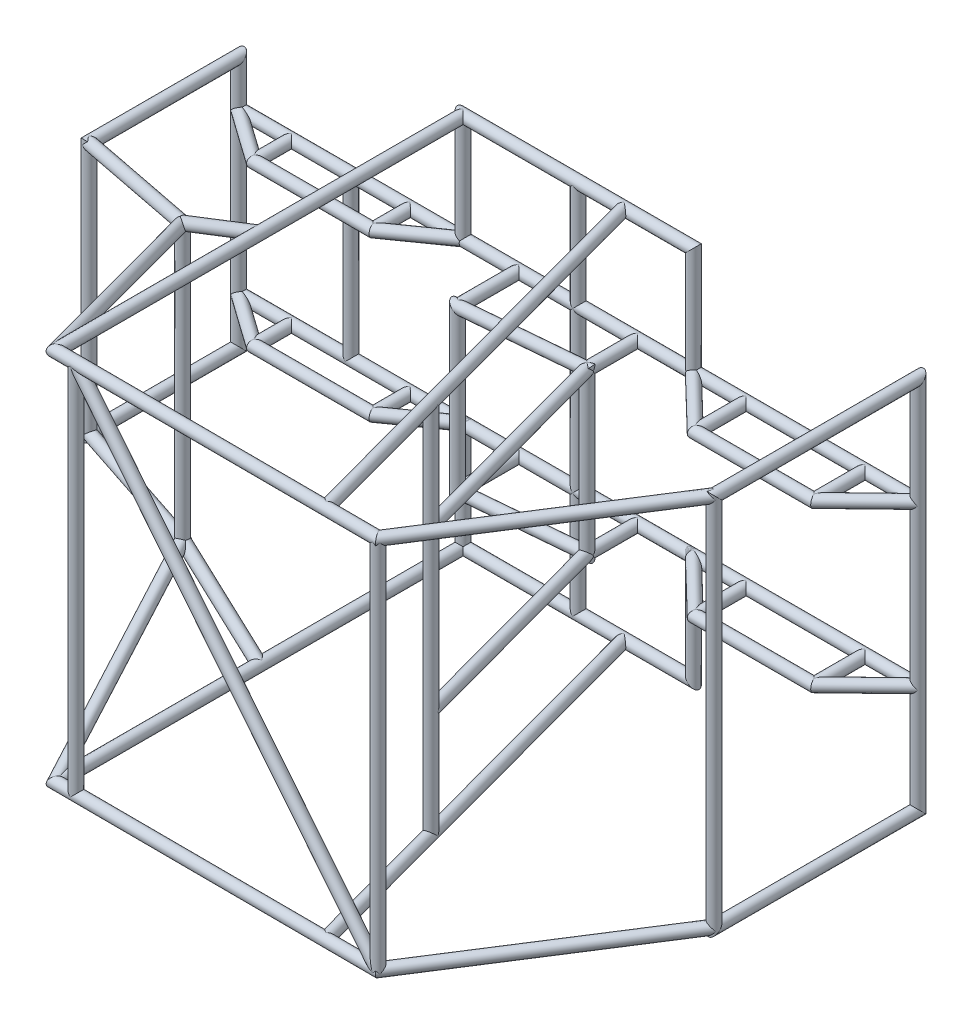
SolidWorks part; units mm, degrees
other "Markup1"
sketch "Sketch117" plane through (1036.7339, -482.8357, 1175.9129) normal (0.0347, -0.967, 0.2524) x (0.9983, 0.0455, 0.0372)
other "Markup2"
sketch "Sketch1172" plane through (1036.7339, -482.8357, 1116.7005) normal (0.0129, -0.9746, 0.2236) x (0.9995, 0.0192, 0.026)
other "Markup3"
sketch "Sketch1173" plane through (-996.6671, 650.5653, 1116.7005) normal (-0.8943, 0.014, 0.4473) x (0.1458, -0.9359, 0.3207)
other "Markup4"
sketch "Sketch1174" plane through (-996.6671, 650.5653, 1116.7005) normal (-0.8943, 0.014, 0.4473) x (0.1458, -0.9359, 0.3207)
other "Markup5"
sketch "Sketch1192" plane through (-996.6671, -482.8357, 1116.7005) normal (-0.3732, -0.8965, 0.2388) x (0.9278, -0.3613, 0.0935)
other "Markup6"
sketch "Sketch1210" plane through (-996.6671, -486.1883, 1216.7017) normal (-0.3761, -0.9216, 0.0957) x (0.9265, -0.373, 0.0487)
material "AISI 1020 Steel, Cold Rolled"
ref_plane "Front Plane" through (0, 0, 0) normal (0, 0, 1) x (1, 0, 0)
ref_plane "Top Plane" through (0, 0, 0) normal (0, 1, 0) x (1, 0, 0)
ref_plane "Right Plane" through (0, 0, 0) normal (1, 0, 0) x (0, 0, -1)
sketch "Sketch1" plane through (0, 0, 0) normal (0, 0, 1) x (1, 0, 0)
  line L1 (1020.0334, 633.8648) -> (1020.0334, -466.1352) construction
  line L4 (-979.9666, -286.1352) -> (-979.9666, 453.8648)
  line L5 (-979.9666, 318.8648) -> (-318.9666, 318.8648)
  line L6 (-318.9666, 318.8648) -> (-318.9666, 633.8648)
  line L7 (-318.9666, 633.8648) -> (359.0334, 633.8648)
  line L8 (359.0334, 633.8648) -> (359.0334, 318.8648)
  line L9 (359.0334, 318.8648) -> (1020.0334, 318.8648)
  line L10 (-979.9666, 83.8648) -> (1020.0334, 83.8648) construction
  line L11 (359.0334, -151.1352) -> (1020.0334, -151.1352)
  line L12 (359.0334, -466.1352) -> (359.0334, -151.1352)
  line L13 (-318.9666, -466.1352) -> (359.0334, -466.1352)
  line L14 (-318.9666, -151.1352) -> (-318.9666, -466.1352)
  line L15 (-979.9666, -151.1352) -> (-318.9666, -151.1352)
  line L18 (1020.0334, 633.8648) -> (1020.0334, -466.1352)
  dimension "D1" = 678
  dimension "D2" = 1100
  dimension "D3" = 315
  dimension "D4" = 661
  dimension "D5" = 661
  dimension "D6" = 315
  dimension "D7" = 370
  dimension "D8" = 370
sketch3d "3DSketch1"
  line L1 (-979.9666, -286.1352, 0) -> (-979.9666, -286.1352, 440)
  line L12 (-979.9666, 453.8648, 0) -> (-979.9666, 453.8648, 440)
  line L14 (1020.0334, -466.1352, 0) -> (1020.0334, -466.1352, 600)
  line L15 (1020.0334, 633.8648, 0) -> (1020.0334, -466.1352, 0) construction
  line L16 (1020.0334, 633.8648, 0) -> (1020.0334, 633.8648, 600)
  line L32 (-318.9666, -466.1352, 0) -> (-318.9666, -466.1352, 1200)
  line L35 (1020.0334, -466.1352, 600) -> (1020.0334, 633.8648, 600)
  line L37 (-318.9666, 633.8648, 0) -> (-318.9666, 633.8648, 1200)
  line L44 (-979.9666, 453.8648, 440) -> (-979.9666, -286.1352, 440)
  line L59 (-318.9666, -466.1352, 0) -> (359.0334, -466.1352, 0) construction
  line L61 (-824.4666, -151.1352, 110) -> (-979.9666, -151.1352, 0)
  line L62 (-649.4666, 318.8648, 0) -> (-649.4666, -151.1352, 0)
  line L63 (-979.9666, 318.8648, 0) -> (-318.9666, 318.8648, 0) construction
  line L64 (-979.9666, -151.1352, 0) -> (-318.9666, -151.1352, 0) construction
  line L65 (359.0334, -151.1352, 0) -> (1020.0334, -151.1352, 0) construction
  line L66 (359.0334, 318.8648, 0) -> (1020.0334, 318.8648, 0) construction
  line L77 (20.0334, -466.1352, 0) -> (20.0334, 633.8648, 0)
  line L78 (-318.9666, 633.8648, 0) -> (359.0334, 633.8648, 0) construction
  line L101 (195.0334, -151.1352, 0) -> (195.0334, -151.1352, 149.379)
  line L102 (-318.9666, -151.1352, 0) -> (359.0334, -151.1352, 0)
  line L103 (195.0334, 318.8648, 0) -> (195.0334, 318.8648, 149.379)
  line L113 (-318.9666, 318.8648, 0) -> (359.0334, 318.8648, 0)
  line L127 (-154.9666, -151.1352, 180) -> (-154.9666, 318.8648, 180)
  line L130 (-154.9666, -151.1352, 0) -> (-154.9666, -151.1352, 180)
  line L131 (-154.9666, 318.8648, 0) -> (-154.9666, 318.8648, 180)
  line L132 (-154.9666, 318.8648, 180) -> (195.0334, 318.8648, 149.379)
  line L133 (-154.9666, -151.1352, 180) -> (195.0334, -151.1352, 149.379)
  line L134 (195.0334, -151.1352, 149.379) -> (195.0334, 318.8648, 149.379)
  line L135 (195.0334, -151.1352, 149.379) -> (195.0334, -151.1352, 921.293) construction
  line L136 (195.0334, 318.8648, 149.379) -> (195.0334, 318.8648, 894.0715) construction
  line L137 (195.0334, -151.1352, 149.379) -> (363.2555, -152.9932, 777.2308)
  line L138 (195.0334, 318.8648, 149.379) -> (363.2555, 317.0068, 777.2308)
  line L144 (-318.9666, -466.1352, 1200) -> (886.7474, -466.1352, 1200) construction
  line L145 (195.0334, 83.8648, 149.379) -> (363.2555, 82.0068, 777.2308) construction
  line L151 (-318.9666, 633.8648, 1200) -> (870.5373, 633.8648, 1200) construction
  line L152 (631.0272, -469.5609, 1200.0013) -> (1020.0334, -466.1352, 600)
  line L153 (631.0272, 630.4391, 1200.0013) -> (1020.0334, 633.8648, 600)
  line L154 (-258.9666, 633.8648, 1200) -> (-258.9666, -466.1352, 1200)
  line L155 (-318.9666, -466.1352, 1200) -> (631.0272, -469.5609, 1200.0013)
  line L156 (-318.9666, 633.8648, 1200) -> (631.0272, 630.4391, 1200.0013)
  line L157 (631.0272, -469.5609, 1200.0013) -> (631.0272, 630.4391, 1200.0013)
  line L158 (-258.9666, 633.8648, 1200) -> (631.0272, -469.5609, 1200.0013)
  line L159 (154.9966, -466.1352, 0) -> (476.5368, -469.0038, 1200.0011)
  line L160 (363.2555, -467.9932, 777.2308) -> (363.2555, 632.0068, 777.2308)
  line L162 (476.5368, 630.9962, 1200.0011) -> (154.9966, 633.8648, 0)
  line L165 (-602.9909, 488.0187, 541.424) -> (-318.9666, 633.8648, 1200)
  line L166 (-602.9933, -320.2889, 541.4234) -> (-318.9666, -466.1352, 1200)
  line L171 (-602.9909, 488.0187, 541.424) -> (-602.9933, -320.2889, 541.4234)
  line L172 (-979.9666, 453.8648, 440) -> (-602.9909, 488.0187, 541.424)
  line L173 (-979.9666, -286.1352, 440) -> (-602.9933, -320.2889, 541.4234)
  line L174 (-602.9933, -320.2889, 541.4234) -> (-318.9666, -466.1352, 600)
  line L175 (-602.9909, 488.0187, 541.424) -> (-318.9666, 633.8648, 600)
  line L178 (-824.4666, -151.1352, 0) -> (-824.4666, -151.1352, 110)
  line L179 (-824.4666, -151.1352, 110) -> (-474.4666, -151.1352, 110)
  line L180 (-474.4666, -151.1352, 110) -> (-474.4666, -151.1352, 0)
  line L181 (-474.4666, 318.8648, 0) -> (-474.4666, 318.8648, 110)
  line L182 (-474.4666, 318.8648, 110) -> (-824.4666, 318.8648, 110)
  line L183 (514.5334, -151.1352, 0) -> (514.5334, -151.1352, 150)
  line L184 (514.5334, -151.1352, 150) -> (864.5334, -151.1352, 150)
  line L185 (864.5334, -151.1352, 150) -> (864.5334, -151.1352, 0)
  line L187 (864.5334, 318.8648, 0) -> (864.5334, 318.8648, 150)
  line L188 (864.5334, 318.8648, 150) -> (514.5334, 318.8648, 150)
  line L189 (514.5334, 318.8648, 150) -> (514.5334, 318.8648, 0)
  line L190 (-824.4666, 318.8648, 110) -> (-824.4666, 318.8648, 0)
  line L191 (-318.9666, 633.8648, 1200) -> (-318.9666, -466.1352, 1200) construction
  line L192 (-474.4666, -151.1352, 110) -> (-318.9666, -151.1352, 0)
  line L193 (514.5334, -151.1352, 150) -> (359.0334, -151.1352, 0)
  line L194 (864.5334, -151.1352, 150) -> (1020.0334, -151.1352, 0)
  line L195 (-824.4666, 318.8648, 110) -> (-979.9666, 318.8648, 0)
  line L196 (-474.4666, 318.8648, 110) -> (-318.9666, 318.8648, 0)
  line L197 (514.5334, 318.8648, 150) -> (359.0334, 318.8648, 0)
  line L198 (864.5334, 318.8648, 150) -> (1020.0334, 318.8648, 0)
  dimension "D3" = 440
  dimension "D2" = 440
  dimension "D9" = 60
  dimension "D4" = 1200
  dimension "D5" = 1200
  dimension "D6" = 60
  dimension "D7" = 600
  dimension "D8" = 600
  dimension "D10" = 1100
  dimension "D15" = 175
  dimension "D11" = 550
  dimension "D12" = 15
  dimension "D13" = 650
  dimension "D14" = 175
  dimension "D18" = 175
  dimension "D16" = 950
  dimension "D17" = 950
  dimension "D19" = 180
  dimension "D35" = 175
  dimension "D26" = 235
  dimension "D29" = 105
  dimension "D28" = 75
  dimension "D20" = 180
  dimension "D21" = 85
  dimension "D22" = 85
  dimension "D23" = 235
  dimension "D24" = 15
  dimension "D25" = 1100
  dimension "D27" = 75
  dimension "D32" = 95
  dimension "D30" = 105
  dimension "D31" = 95
  dimension "D33" = 391.87
  dimension "D34" = 350
  dimension "D36" = 150
  dimension "D45" = 110
  dimension "D39" = 110
  dimension "D37" = 350
  dimension "D40" = 175
  dimension "D41" = 350
  dimension "D42" = 150
  dimension "D43" = 350
other "Pipe 1.0 SCH 40(15)" corner treatment miter
ref_plane "Plane17" through (-979.9666, -151.1352, 0) normal (1, 0, 0) x (0, 1, 0)
sketch "Sketch1171" plane through (-979.9666, -151.1352, 0) normal (1, 0, 0) x (0, 1, 0)
  circle A0 centre (0, 0) radius 13.3223
  circle A1 centre (0, 0) radius 16.7005
  circle A2 centre (0, 0) radius 12.7 construction
  point P5 (0, 16.7005)
  point P6 (0, -16.7005)
  point P7 (-16.7005, 0)
  point P8 (16.7005, 0)
  point P9 (0, 0)
  dimension "In_dia" = 26.6446
  dimension "Out_dia" = 33.401
  dimension "D1" = 25.4
other "Pipe 1.0 SCH 40(16)" corner treatment miter
ref_plane "Plane18" through (-979.9666, 318.8648, 0) normal (1, 0, 0) x (0, 1, 0)
sketch "Sketch118" plane through (-979.9666, 318.8648, 0) normal (1, 0, 0) x (0, 1, 0)
  circle A0 centre (0, 0) radius 13.3223
  circle A1 centre (0, 0) radius 16.7005
  circle A2 centre (0, 0) radius 12.7 construction
  point P5 (0, 16.7005)
  point P6 (0, -16.7005)
  point P7 (-16.7005, 0)
  point P8 (16.7005, 0)
  point P9 (0, 0)
  dimension "In_dia" = 26.6446
  dimension "Out_dia" = 33.401
  dimension "D1" = 25.4
other "Pipe 1.0 SCH 40(18)" corner treatment miter
ref_plane "Plane20" through (-979.9666, -286.1352, 0) normal (0, 0, 1) x (1, 0, 0)
sketch "Sketch120" plane through (-979.9666, -286.1352, 0) normal (0, 0, 1) x (1, 0, 0)
  circle A0 centre (0, 0) radius 13.3223
  circle A1 centre (0, 0) radius 16.7005
  circle A2 centre (0, 0) radius 12.7 construction
  point P5 (0, 16.7005)
  point P6 (0, -16.7005)
  point P7 (-16.7005, 0)
  point P8 (16.7005, 0)
  point P9 (0, 0)
  dimension "In_dia" = 26.6446
  dimension "Out_dia" = 33.401
  dimension "D1" = 25.4
other "Pipe 1.0 SCH 40(19)" corner treatment miter
ref_plane "Plane21" through (1020.0334, -466.1352, 0) normal (0, 0, 1) x (1, 0, 0)
sketch "Sketch121" plane through (1020.0334, -466.1352, 0) normal (0, 0, 1) x (1, 0, 0)
  circle A0 centre (0, 0) radius 13.3223
  circle A1 centre (0, 0) radius 16.7005
  circle A2 centre (0, 0) radius 12.7 construction
  point P5 (0, 16.7005)
  point P6 (0, -16.7005)
  point P7 (-16.7005, 0)
  point P8 (16.7005, 0)
  point P9 (0, 0)
  dimension "In_dia" = 26.6446
  dimension "Out_dia" = 33.401
  dimension "D1" = 25.4
other "Pipe 1.0 SCH 40(30)" corner treatment miter
ref_plane "Plane34" through (20.0334, -466.1352, 0) normal (0, 1, 0) x (1, 0, 0)
sketch "Sketch134" plane through (20.0334, -466.1352, 0) normal (0, 1, 0) x (1, 0, 0)
  circle A0 centre (0, 0) radius 13.3223
  circle A1 centre (0, 0) radius 16.7005
  circle A2 centre (0, 0) radius 12.7 construction
  point P5 (0, 16.7005)
  point P6 (0, -16.7005)
  point P7 (-16.7005, 0)
  point P8 (16.7005, 0)
  point P9 (0, 0)
  dimension "In_dia" = 26.6446
  dimension "Out_dia" = 33.401
  dimension "D1" = 25.4
other "Pipe 1.0 SCH 40(107)" corner treatment miter
ref_plane "Plane57" through (-318.9666, 633.8648, 0) normal (0, 0, 1) x (1, 0, 0)
sketch "Sketch1186" plane through (-318.9666, 633.8648, 0) normal (0, 0, 1) x (1, 0, 0)
  circle A0 centre (0, 0) radius 13.3223
  circle A1 centre (0, 0) radius 16.7005
  circle A2 centre (0, 0) radius 12.7 construction
  point P5 (0, 16.7005)
  point P6 (0, -16.7005)
  point P7 (-16.7005, 0)
  point P8 (16.7005, 0)
  point P9 (0, 0)
  dimension "In_dia" = 26.6446
  dimension "Out_dia" = 33.401
  dimension "D1" = 25.4
other "Pipe 1.0 SCH 40(108)" corner treatment miter
ref_plane "Plane58" through (-318.9666, -151.1352, 0) normal (1, 0, 0) x (0, 0, -1)
sketch "Sketch1187" plane through (-318.9666, -151.1352, 0) normal (1, 0, 0) x (0, 0, -1)
  circle A0 centre (0, 0) radius 13.3223
  circle A1 centre (0, 0) radius 16.7005
  circle A2 centre (0, 0) radius 12.7 construction
  point P5 (0, 16.7005)
  point P6 (0, -16.7005)
  point P7 (-16.7005, 0)
  point P8 (16.7005, 0)
  point P9 (0, 0)
  dimension "In_dia" = 26.6446
  dimension "Out_dia" = 33.401
  dimension "D1" = 25.4
other "Pipe 1.0 SCH 40(109)" corner treatment miter
ref_plane "Plane59" through (-154.9666, -151.1352, 180) normal (0.9962, 0, -0.0872) x (-0.0872, 0, -0.9962)
sketch "Sketch1188" plane through (-154.9666, -151.1352, 180) normal (0.9962, 0, -0.0872) x (-0.0872, 0, -0.9962)
  circle A0 centre (0, 0) radius 13.3223
  circle A1 centre (0, 0) radius 16.7005
  circle A2 centre (0, 0) radius 12.7 construction
  point P5 (0, 16.7005)
  point P6 (0, -16.7005)
  point P7 (-16.7005, 0)
  point P8 (16.7005, 0)
  point P9 (0, 0)
  dimension "In_dia" = 26.6446
  dimension "Out_dia" = 33.401
  dimension "D1" = 25.4
other "Pipe 1.0 SCH 40(168)" corner treatment miter
ref_plane "Plane67" through (-154.9666, -151.1352, 0) normal (0, 0, 1) x (1, 0, 0)
sketch "Sketch1198" plane through (-154.9666, -151.1352, 0) normal (0, 0, 1) x (1, 0, 0)
  circle A0 centre (0, 0) radius 13.3223
  circle A1 centre (0, 0) radius 16.7005
  circle A2 centre (0, 0) radius 12.7 construction
  point P5 (0, 16.7005)
  point P6 (0, -16.7005)
  point P7 (-16.7005, 0)
  point P8 (16.7005, 0)
  point P9 (0, 0)
  dimension "In_dia" = 26.6446
  dimension "Out_dia" = 33.401
  dimension "D1" = 25.4
other "Pipe 1.0 SCH 40(207)" corner treatment miter
ref_plane "Plane70" through (-258.9666, 633.8648, 1200) normal (0, -1, 0) x (1, 0, 0)
sketch "Sketch1202" plane through (-258.9666, 633.8648, 1200) normal (0, -1, 0) x (1, 0, 0)
  circle A0 centre (0, 0) radius 13.3223
  circle A1 centre (0, 0) radius 16.7005
  circle A2 centre (0, 0) radius 12.7 construction
  point P5 (0, 16.7005)
  point P6 (0, -16.7005)
  point P7 (-16.7005, 0)
  point P8 (16.7005, 0)
  point P9 (0, 0)
  dimension "In_dia" = 26.6446
  dimension "Out_dia" = 33.401
  dimension "D1" = 25.4
other "Pipe 1.0 SCH 40(208)" corner treatment miter
ref_plane "Plane71" through (-258.9666, 633.8648, 1200) normal (0.6278, -0.7784, 0) x (0.6059, 0.4887, -0.6278)
sketch "Sketch1203" plane through (-258.9666, 633.8648, 1200) normal (0.6278, -0.7784, 0) x (0.6059, 0.4887, -0.6278)
  circle A0 centre (0, 0) radius 13.3223
  circle A1 centre (0, 0) radius 16.7005
  circle A2 centre (0, 0) radius 12.7 construction
  point P5 (0, 16.7005)
  point P6 (0, -16.7005)
  point P7 (-16.7005, 0)
  point P8 (16.7005, 0)
  point P9 (0, 0)
  dimension "In_dia" = 26.6446
  dimension "Out_dia" = 33.401
  dimension "D1" = 25.4
other "Pipe 1.0 SCH 40(209)" corner treatment miter
ref_plane "Plane72" through (476.5368, 630.9962, 1200.0011) normal (-0.2588, 0.0023, -0.9659) x (-0.9658, 0.0175, 0.2588)
sketch "Sketch1204" plane through (476.5368, 630.9962, 1200.0011) normal (-0.2588, 0.0023, -0.9659) x (-0.9658, 0.0175, 0.2588)
  circle A0 centre (0, 0) radius 13.3223
  circle A1 centre (0, 0) radius 16.7005
  circle A2 centre (0, 0) radius 12.7 construction
  point P5 (0, 16.7005)
  point P6 (0, -16.7005)
  point P7 (-16.7005, 0)
  point P8 (16.7005, 0)
  point P9 (0, 0)
  dimension "In_dia" = 26.6446
  dimension "Out_dia" = 33.401
  dimension "D1" = 25.4
other "Pipe 1.0 SCH 40(210)" corner treatment miter
ref_plane "Plane73" through (363.2555, -467.9932, 777.2308) normal (0, 1, 0) x (1, 0, 0)
sketch "Sketch1205" plane through (363.2555, -467.9932, 777.2308) normal (0, 1, 0) x (1, 0, 0)
  circle A0 centre (0, 0) radius 13.3223
  circle A1 centre (0, 0) radius 16.7005
  circle A2 centre (0, 0) radius 12.7 construction
  point P5 (0, 16.7005)
  point P6 (0, -16.7005)
  point P7 (-16.7005, 0)
  point P8 (16.7005, 0)
  point P9 (0, 0)
  dimension "In_dia" = 26.6446
  dimension "Out_dia" = 33.401
  dimension "D1" = 25.4
other "Pipe 1.0 SCH 40(234)" corner treatment miter
ref_plane "Plane74" through (195.0334, 318.8648, 149.379) normal (0.2588, -0.0029, 0.9659) x (0.9659, 0.0004, -0.2588)
sketch "Sketch1207" plane through (195.0334, 318.8648, 149.379) normal (0.2588, -0.0029, 0.9659) x (0.9659, 0.0004, -0.2588)
  circle A0 centre (0, 0) radius 13.3223
  circle A1 centre (0, 0) radius 16.7005
  circle A2 centre (0, 0) radius 12.7 construction
  point P5 (0, 16.7005)
  point P6 (0, -16.7005)
  point P7 (-16.7005, 0)
  point P8 (16.7005, 0)
  point P9 (0, 0)
  dimension "In_dia" = 26.6446
  dimension "Out_dia" = 33.401
  dimension "D1" = 25.4
other "Pipe 1.0 SCH 40(235)" corner treatment miter
ref_plane "Plane75" through (195.0334, -151.1352, 149.379) normal (0.2588, -0.0029, 0.9659) x (0.9659, 0.0004, -0.2588)
sketch "Sketch1208" plane through (195.0334, -151.1352, 149.379) normal (0.2588, -0.0029, 0.9659) x (0.9659, 0.0004, -0.2588)
  circle A0 centre (0, 0) radius 13.3223
  circle A1 centre (0, 0) radius 16.7005
  circle A2 centre (0, 0) radius 12.7 construction
  point P5 (0, 16.7005)
  point P6 (0, -16.7005)
  point P7 (-16.7005, 0)
  point P8 (16.7005, 0)
  point P9 (0, 0)
  dimension "In_dia" = 26.6446
  dimension "Out_dia" = 33.401
  dimension "D1" = 25.4
other "Pipe 1.0 SCH 40(351)" corner treatment miter
ref_plane "Plane76" through (-979.9666, -286.1352, 440) normal (0.962, -0.0872, 0.2588) x (0.2649, 0.0666, -0.962)
sketch "Sketch1212" plane through (-979.9666, -286.1352, 440) normal (0.962, -0.0872, 0.2588) x (0.2649, 0.0666, -0.962)
  circle A0 centre (0, 0) radius 13.3223
  circle A1 centre (0, 0) radius 16.7005
  circle A2 centre (0, 0) radius 12.7 construction
  point P5 (0, 16.7005)
  point P6 (0, -16.7005)
  point P7 (-16.7005, 0)
  point P8 (16.7005, 0)
  point P9 (0, 0)
  dimension "In_dia" = 26.6446
  dimension "Out_dia" = 33.401
  dimension "D1" = 25.4
other "Pipe 1.0 SCH 40(352)" corner treatment miter
ref_plane "Plane77" through (-979.9666, 453.8648, 440) normal (0.962, 0.0872, 0.2588) x (0.2649, -0.0666, -0.962)
sketch "Sketch1213" plane through (-979.9666, 453.8648, 440) normal (0.962, 0.0872, 0.2588) x (0.2649, -0.0666, -0.962)
  circle A0 centre (0, 0) radius 13.3223
  circle A1 centre (0, 0) radius 16.7005
  circle A2 centre (0, 0) radius 12.7 construction
  point P5 (0, 16.7005)
  point P6 (0, -16.7005)
  point P7 (-16.7005, 0)
  point P8 (16.7005, 0)
  point P9 (0, 0)
  dimension "In_dia" = 26.6446
  dimension "Out_dia" = 33.401
  dimension "D1" = 25.4
other "Pipe 1.0 SCH 40(353)" corner treatment miter
ref_plane "Plane78" through (-602.9909, 488.0187, 541.424) normal (0, -1, 0) x (1, 0, 0)
sketch "Sketch1214" plane through (-602.9909, 488.0187, 541.424) normal (0, -1, 0) x (1, 0, 0)
  circle A0 centre (0, 0) radius 13.3223
  circle A1 centre (0, 0) radius 16.7005
  circle A2 centre (0, 0) radius 12.7 construction
  point P5 (0, 16.7005)
  point P6 (0, -16.7005)
  point P7 (-16.7005, 0)
  point P8 (16.7005, 0)
  point P9 (0, 0)
  dimension "In_dia" = 26.6446
  dimension "Out_dia" = 33.401
  dimension "D1" = 25.4
other "Pipe 1.0 SCH 40(368)" corner treatment miter
ref_plane "Plane79" through (-602.9933, -320.2889, 541.4234) normal (0.875, -0.4493, 0.1805) x (0.3515, 0.333, -0.875)
sketch "Sketch1215" plane through (-602.9933, -320.2889, 541.4234) normal (0.875, -0.4493, 0.1805) x (0.3515, 0.333, -0.875)
  circle A0 centre (0, 0) radius 13.3223
  circle A1 centre (0, 0) radius 16.7005
  circle A2 centre (0, 0) radius 12.7 construction
  point P5 (0, 16.7005)
  point P6 (0, -16.7005)
  point P7 (-16.7005, 0)
  point P8 (16.7005, 0)
  point P9 (0, 0)
  dimension "In_dia" = 26.6446
  dimension "Out_dia" = 33.401
  dimension "D1" = 25.4
other "Pipe 1.0 SCH 40(369)" corner treatment miter
ref_plane "Plane80" through (-602.9909, 488.0187, 541.424) normal (0.875, 0.4493, 0.1804) x (0.3515, -0.333, -0.875)
sketch "Sketch1216" plane through (-602.9909, 488.0187, 541.424) normal (0.875, 0.4493, 0.1804) x (0.3515, -0.333, -0.875)
  circle A0 centre (0, 0) radius 13.3223
  circle A1 centre (0, 0) radius 16.7005
  circle A2 centre (0, 0) radius 12.7 construction
  point P5 (0, 16.7005)
  point P6 (0, -16.7005)
  point P7 (-16.7005, 0)
  point P8 (16.7005, 0)
  point P9 (0, 0)
  dimension "In_dia" = 26.6446
  dimension "Out_dia" = 33.401
  dimension "D1" = 25.4
ref_plane "Plane86" through (-649.4666, 318.8648, 0) normal (0, -1, 0) x (1, 0, 0)
other "Pipe 1.0 SCH 40(501)" corner treatment miter
ref_plane "Plane87" through (-649.4666, 318.8648, 0) normal (0, -1, 0) x (1, 0, 0)
sketch "Sketch1225" plane through (-649.4666, 318.8648, 0) normal (0, -1, 0) x (1, 0, 0)
  circle A0 centre (0, 0) radius 13.3223
  circle A1 centre (0, 0) radius 16.7005
  circle A2 centre (0, 0) radius 12.7 construction
  point P5 (0, 16.7005)
  point P6 (0, -16.7005)
  point P7 (-16.7005, 0)
  point P8 (16.7005, 0)
  point P9 (0, 0)
  dimension "In_dia" = 26.6446
  dimension "Out_dia" = 33.401
  dimension "D1" = 25.4
other "Pipe 1.0 SCH 40(533)" corner treatment miter
ref_plane "Plane92" through (-824.4666, 318.8648, 110) normal (-0.8164, 0, -0.5775) x (-0.5775, 0, 0.8164)
sketch "Sketch1231" plane through (-824.4666, 318.8648, 110) normal (-0.8164, 0, -0.5775) x (-0.5775, 0, 0.8164)
  circle A0 centre (0, 0) radius 13.3223
  circle A1 centre (0, 0) radius 16.7005
  circle A2 centre (0, 0) radius 12.7 construction
  point P5 (0, 16.7005)
  point P6 (0, -16.7005)
  point P7 (-16.7005, 0)
  point P8 (16.7005, 0)
  point P9 (0, 0)
  dimension "In_dia" = 26.6446
  dimension "Out_dia" = 33.401
  dimension "D1" = 25.4
other "Pipe 1.0 SCH 40(534)" corner treatment miter
ref_plane "Plane93" through (-824.4666, -151.1352, 110) normal (-0.8164, 0, -0.5775) x (-0.5775, 0, 0.8164)
sketch "Sketch1232" plane through (-824.4666, -151.1352, 110) normal (-0.8164, 0, -0.5775) x (-0.5775, 0, 0.8164)
  circle A0 centre (0, 0) radius 13.3223
  circle A1 centre (0, 0) radius 16.7005
  circle A2 centre (0, 0) radius 12.7 construction
  point P5 (0, 16.7005)
  point P6 (0, -16.7005)
  point P7 (-16.7005, 0)
  point P8 (16.7005, 0)
  point P9 (0, 0)
  dimension "In_dia" = 26.6446
  dimension "Out_dia" = 33.401
  dimension "D1" = 25.4
other "Pipe 1.0 SCH 40(535)" corner treatment miter
ref_plane "Plane94" through (514.5334, 318.8648, 150) normal (-0.7197, 0, -0.6943) x (-0.6943, 0, 0.7197)
sketch "Sketch1233" plane through (514.5334, 318.8648, 150) normal (-0.7197, 0, -0.6943) x (-0.6943, 0, 0.7197)
  circle A0 centre (0, 0) radius 13.3223
  circle A1 centre (0, 0) radius 16.7005
  circle A2 centre (0, 0) radius 12.7 construction
  point P5 (0, 16.7005)
  point P6 (0, -16.7005)
  point P7 (-16.7005, 0)
  point P8 (16.7005, 0)
  point P9 (0, 0)
  dimension "In_dia" = 26.6446
  dimension "Out_dia" = 33.401
  dimension "D1" = 25.4
other "Pipe 1.0 SCH 40(536)" corner treatment miter
ref_plane "Plane95" through (514.5334, -151.1352, 150) normal (-0.7197, 0, -0.6943) x (-0.6943, 0, 0.7197)
sketch "Sketch1234" plane through (514.5334, -151.1352, 150) normal (-0.7197, 0, -0.6943) x (-0.6943, 0, 0.7197)
  circle A0 centre (0, 0) radius 13.3223
  circle A1 centre (0, 0) radius 16.7005
  circle A2 centre (0, 0) radius 12.7 construction
  point P5 (0, 16.7005)
  point P6 (0, -16.7005)
  point P7 (-16.7005, 0)
  point P8 (16.7005, 0)
  point P9 (0, 0)
  dimension "In_dia" = 26.6446
  dimension "Out_dia" = 33.401
  dimension "D1" = 25.4
other "Pipe 1.0 SCH 40(537)" corner treatment miter
ref_plane "Plane96" through (-824.4666, 318.8648, 110) normal (0, 0, -1) x (1, 0, 0)
sketch "Sketch1235" plane through (-824.4666, 318.8648, 110) normal (0, 0, -1) x (1, 0, 0)
  circle A0 centre (0, 0) radius 13.3223
  circle A1 centre (0, 0) radius 16.7005
  circle A2 centre (0, 0) radius 12.7 construction
  point P5 (0, 16.7005)
  point P6 (0, -16.7005)
  point P7 (-16.7005, 0)
  point P8 (16.7005, 0)
  point P9 (0, 0)
  dimension "In_dia" = 26.6446
  dimension "Out_dia" = 33.401
  dimension "D1" = 25.4
